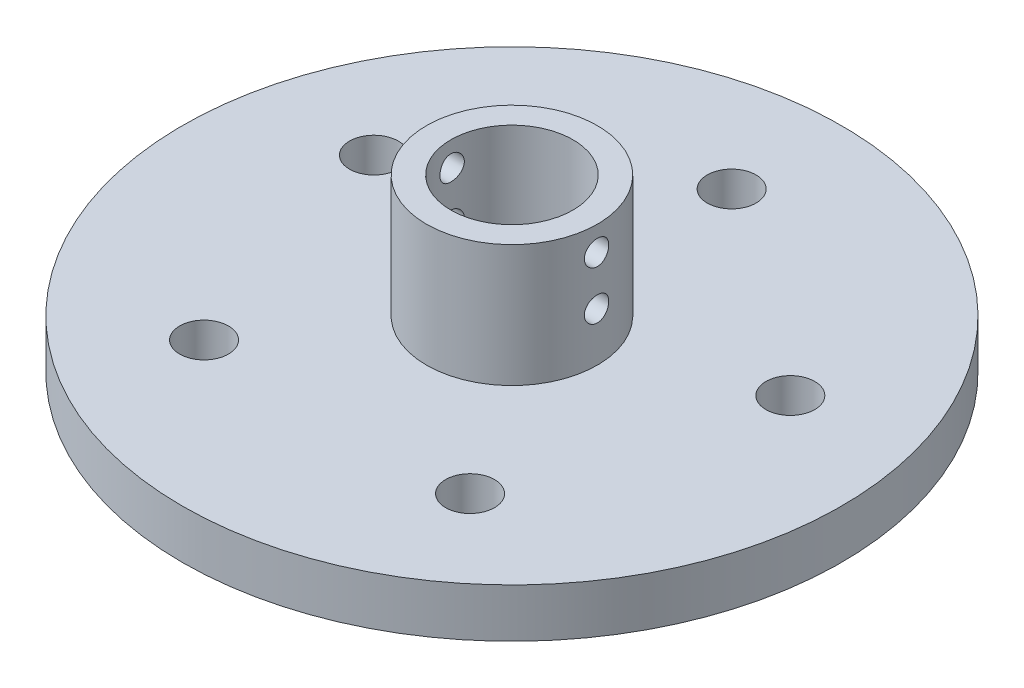
SolidWorks part; units mm, degrees
material "Delrin 2700 NC010, Low Viscosity Acetal Copolymer (SS)"
ref_plane "Front Plane" through (0, 0, 0) normal (0, 0, 1) x (1, 0, 0)
ref_plane "Top Plane" through (0, 0, 0) normal (0, 1, 0) x (1, 0, 0)
ref_plane "Right Plane" through (0, 0, 0) normal (1, 0, 0) x (0, 0, -1)
sketch "Sketch1" plane through (0, 0, 0) normal (0, 0, 1) x (1, 0, 0)
  line L0 (0, 7.8095) -> (0, 0) construction
  line L1 (0, 0) -> (15.875, 0) construction
  line L3 (15.875, 0) -> (85.725, 0)
  line L4 (15.875, 0) -> (15.875, 12.7)
  line L5 (15.875, 12.7) -> (85.725, 12.7)
  line L6 (85.725, 0) -> (85.725, 12.7)
  line L7 (15.875, 12.7) -> (22.225, 12.7)
  line L8 (15.875, 12.7) -> (15.875, 44.45)
  line L9 (15.875, 44.45) -> (22.225, 44.45)
  line L10 (22.225, 12.7) -> (22.225, 44.45)
  dimension "D1" = 15.875
  dimension "D2" = 12.7
  dimension "D3" = 6.35
  dimension "D4" = 31.75
  dimension "5.5" = 69.85
revolve "Revolve1" add sketch "Sketch1" angle 360 about L0 region at (50.8, 6.35, 0) region at (19.05, 28.575, 0)
sketch "Sketch2" plane through (0, 12.7, 0) normal (0, 1, 0) x (1, 0, 0)
  line L0 (0, 57.15) -> (54.1556, 18.2562) construction
  line L1 (54.1556, 18.2562) -> (34.5994, -45.4863) construction
  line L2 (34.5994, -45.4863) -> (-34.5994, -45.4863) construction
  line L3 (-34.5994, -45.4863) -> (-54.1556, 18.2562) construction
  line L4 (-54.1556, 18.2562) -> (0, 57.15) construction
  circle A0 centre (0, 0) radius 57.15 construction
  point P3 (-54.1556, 18.2562)
  point P4 (0, 57.15)
  point P5 (54.1556, 18.2562)
  point P6 (-34.5994, -45.4863)
  point P7 (34.5994, -45.4863)
  dimension "D1" = 114.3
  dimension "D2" = 66.675
hole_wizard "1/2-20 Tapped Hole1" positions "Sketch3" profile "Sketch4" tap size "1/2-20" standard "ANSI Inch" end condition through all
sketch "Sketch3" plane through (0, 12.7, 0) normal (0, 1, 0) x (1, 0, 0)
  point P0 (-54.1556, 18.2562)
  point P3 (0, 57.15)
  point P6 (54.1556, 18.2562)
  point P9 (34.5994, -45.4863)
  point P12 (-34.5994, -45.4863)
sketch "Sketch4" plane through (-54.1556, 12.7, -18.2562) normal (1, 0, 0) x (0, 0, 1)
  line L0 (0, 0) -> (0, 12.7)
  line L1 (0, 12.7) -> (6.35, 12.7)
  line L2 (6.35, 12.7) -> (6.35, 0)
  line L5 (6.35, 0) -> (0, 0)
  line L11 (0, -6.35) -> (0, 107.95) construction
  dimension "Thru Tap Drill Dia." = 12.7
  dimension "Thru Tap Drill Depth" = 12.7
cosmetic thread "Hole Thread1" parameters "D2"=12.7
cosmetic thread "Hole Thread2" parameters "D2"=12.7
cosmetic thread "Hole Thread4" parameters "D2"=12.7
cosmetic thread "Hole Thread5" parameters "D2"=12.7
cosmetic thread "Hole Thread6" parameters "D2"=12.7
hole_wizard "1/4 (0.25) Diameter Hole1" positions "Sketch6" profile "Sketch7" hole size "1/4" standard "ANSI Inch" end condition through all
sketch "Sketch6" plane through (0, 0, 0) normal (1, 0, 0) x (0, 0, -1)
  point P0 (0, 38.1)
  point P5 (0, 25.4)
  dimension "D1" = 38.1
  dimension "D2" = 25.4
sketch "Sketch7" plane through (0, 38.1, 0) normal (0, 1, 0) x (0, 0, 1)
  line L0 (0, 0) -> (0, 85.725)
  line L1 (0, 85.725) -> (3.175, 85.725)
  line L2 (3.175, 85.725) -> (3.175, 0)
  line L5 (3.175, 0) -> (0, 0)
  line L11 (0, -6.35) -> (0, 107.95) construction
  dimension "Thru Hole Dia." = 6.35
  dimension "Thru Hole Depth" = 85.725
hole_wizard "1/4 (0.25) Diameter Hole2" positions "Sketch8" profile "Sketch9" hole size "1/4" standard "ANSI Inch" end condition through all
sketch "Sketch8" plane through (0, 0, 0) normal (1, 0, 0) x (0, 0, -1)
  point P3 (0, 38.1)
  point P6 (0, 25.4)
sketch "Sketch9" plane through (0, 38.1, 0) normal (0, 1, 0) x (0, 0, -1)
  line L0 (0, 0) -> (0, 85.725)
  line L1 (0, 85.725) -> (3.175, 85.725)
  line L2 (3.175, 85.725) -> (3.175, 0)
  line L5 (3.175, 0) -> (0, 0)
  line L11 (0, -6.35) -> (0, 107.95) construction
  dimension "Thru Hole Dia." = 6.35
  dimension "Thru Hole Depth" = 85.725
